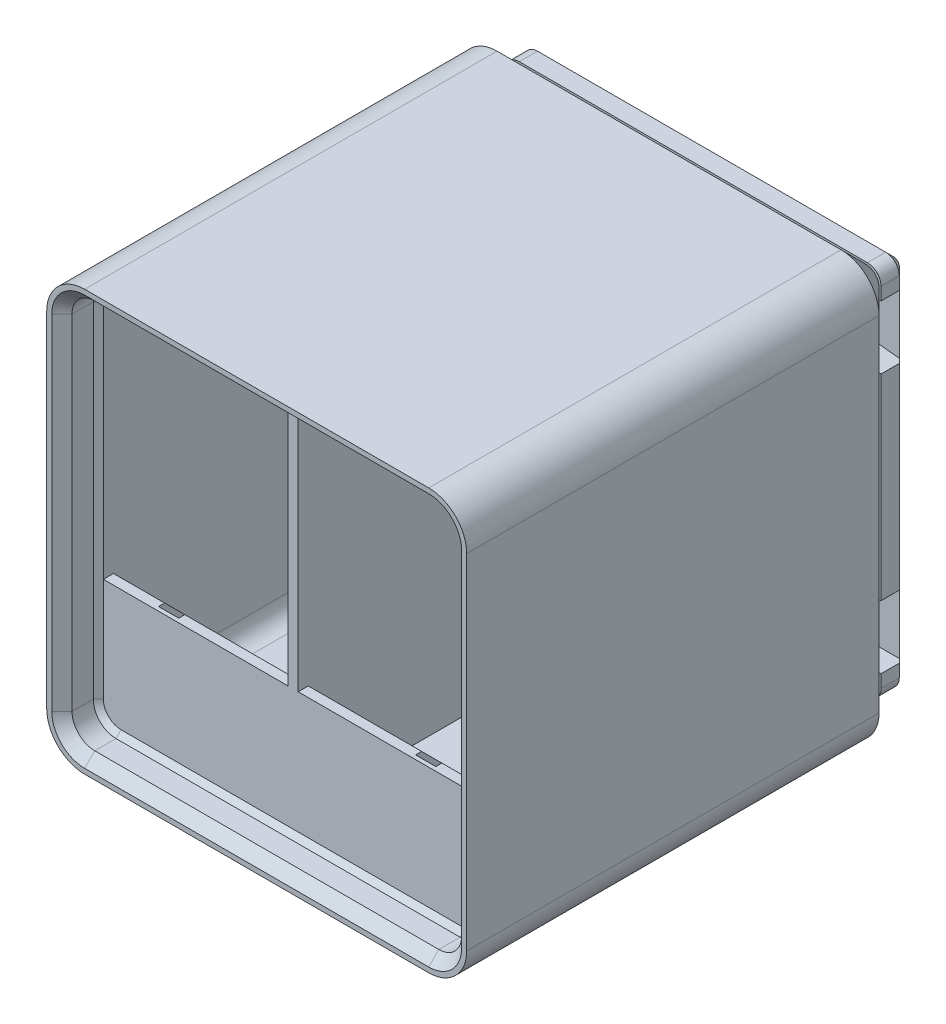
SolidWorks part; units mm, degrees
ref_plane "Front Plane" through (0, 0, 0) normal (0, 0, 1) x (1, 0, 0)
ref_plane "Top Plane" through (0, 0, 0) normal (0, 1, 0) x (1, 0, 0)
ref_plane "Right Plane" through (0, 0, 0) normal (1, 0, 0) x (0, 0, -1)
sketch "Sketch1" plane through (0, 0, 0) normal (0, 0, 1) x (1, 0, 0)
  line L1 (18.55, 18.55) -> (-18.55, 18.55)
  line L2 (18.55, 18.55) -> (18.55, -18.55)
  line L3 (18.55, -18.55) -> (-18.55, -18.55)
  line L4 (-18.55, 18.55) -> (-18.55, -18.55)
  line L5 (18.55, 18.55) -> (-18.55, -18.55) construction
  line L6 (18.55, -18.55) -> (-18.55, 18.55) construction
  point P0 (0, 0)
  dimension "D1" = 37.1
extrude "Boss-Extrude1" add sketch "Sketch1" along normal blind 2.6
sketch "Sketch2" plane through (0, 0, 2.6) normal (0, 0, 1) x (1, 0, 0)
  line L1 (-20.75, 20.75) -> (20.75, 20.75)
  line L2 (-20.75, 20.75) -> (-20.75, -20.75)
  line L3 (-20.75, -20.75) -> (20.75, -20.75)
  line L4 (20.75, 20.75) -> (20.75, -20.75)
  line L5 (-20.75, 20.75) -> (20.75, -20.75) construction
  line L6 (-20.75, -20.75) -> (20.75, 20.75) construction
  point P0 (0, 0)
  dimension "D1" = 41.5
extrude "Boss-Extrude2" add sketch "Sketch2" along normal blind 2.4
sketch "Sketch8" plane through (0, 0, 2.6) normal (0, 0, -1) x (-1, 0, 0)
  line L0 (-18.55, 18.55) -> (-18.55, 5.0094) construction
  line L1 (-18.55, -18.55) -> (-18.55, 18.55) construction
  line L2 (-14.65, 10.1) -> (-18.55, 9.7)
  line L11 (-12.7, 15.95) -> (-18.55, 15.95)
  line L12 (-12.7, 12.7) -> (-12.7, -12.7)
  line L13 (-12.7, -12.7) -> (12.7, -12.7)
  line L14 (12.7, -12.7) -> (12.7, 12.7)
  line L15 (12.7, 12.7) -> (-12.7, 12.7)
  line L16 (-12.7, 9.45) -> (-12.7, -12.7) construction
  line L22 (-18.55, 15.95) -> (-18.55, 9.7)
  arc A0 (-12.7, 15.95) -> (-12.7, 9.45) centre (-12.7, 12.7) cw
  arc A1 (-12.7, 9.45) -> (-14.65, 10.1) centre (-12.7, 12.7) cw
  dimension "D4" = 5.85
  dimension "D5" = 6.25
  dimension "D2" = 6.5
  dimension "D1" = 8.05
extrude "Base Magnet Slot" cut sketch "Sketch8" against normal blind 0.4 and the other way blind 2.2
sketch "Sketch12" plane through (0, 0, 0) normal (0, 0, -1) x (-1, 0, 0)
  line L0 (-12.7, 12.7) -> (-6.2, 12.7) construction
  line L1 (-12.7, 13.7) -> (-6.2, 13.7)
  line L2 (-12.7, 11.7) -> (-6.2, 11.7)
  arc A8 (-14.65, 10.1) -> (-12.7, 15.95) centre (-12.7, 12.7) ccw construction
  arc A9 (-14.65, 10.1) -> (-12.7, 15.95) centre (-12.7, 12.7) ccw construction
  arc A10 (-12.7, 13.7) -> (-12.7, 11.7) centre (-12.7, 12.7) ccw
  arc A11 (-6.2, 11.7) -> (-6.2, 13.7) centre (-6.2, 12.7) ccw
  point P3 (-9.45, 12.7)
  dimension "D1" = 2
  dimension "D2" = 6.5
extrude "Cut-Extrude1" cut sketch "Sketch12" against normal up to surface (2.6 mm away) up to face at (0, 0, 2.6)
mirror "Mirror1" about plane through (0, 0, 0) normal (0, 1, 0) of "Cut-Extrude1", "Base Magnet Slot"
mirror "Mirror2" about plane through (0, 0, 0) normal (1, 0, 0) of "Mirror1"
fillet "Fillet1" radius 1.35 4 edges at (18.55, 18.55, 1.3) (18.55, -18.55, 1.3) (-18.55, -18.55, 1.3) (-18.55, 18.55, 1.3)
fillet "Fillet2" radius 3.75 4 edges at (20.75, -20.75, 3.8) (20.75, 20.75, 3.8) (-20.75, -20.75, 3.8) (-20.75, 20.75, 3.8)
chamfer "Chamfer1" distance 0.8 angle 45 8 edges at (-18.1546, 18.1546, 0) (-18.55, 0, 0) (-18.1546, -18.1546, 0) (0, -18.55, 0) (18.1546, -18.1546, 0) (18.55, 0, 0) (18.1546, 18.1546, 0) (0, 18.55, 0)
chamfer "Chamfer2" distance 2.4 angle 45 8 edges at (20.75, 0, 2.6) (19.6517, 19.6517, 2.6) (19.6517, -19.6517, 2.6) (0, 20.75, 2.6) (0, -20.75, 2.6) (-19.6517, 19.6517, 2.6) (-19.6517, -19.6517, 2.6) (-20.75, 0, 2.6)
sketch "Sketch5" plane through (0, 0, 5) normal (0, 0, 1) x (1, 0, 0)
  line L32 (-17, -18.75) -> (17, -18.75)
  line L33 (18.75, -17) -> (18.75, 17)
  line L42 (17, 18.75) -> (-17, 18.75)
  line L56 (-18.75, 17) -> (-18.75, -17)
  line L57 (-17, -20.75) -> (17, -20.75)
  line L58 (20.75, -17) -> (20.75, 17)
  line L59 (17, 20.75) -> (-17, 20.75)
  line L60 (-20.75, 17) -> (-20.75, -17)
  line L61 (-17, -20.75) -> (17, -20.75)
  line L62 (20.75, -17) -> (20.75, 17)
  line L63 (17, 20.75) -> (-17, 20.75)
  line L64 (-20.75, 17) -> (-20.75, -17)
  arc A24 (17, -18.75) -> (18.75, -17) centre (17, -17) ccw
  arc A25 (18.75, 17) -> (17, 18.75) centre (17, 17) ccw
  arc A26 (-17, 18.75) -> (-18.75, 17) centre (-17, 17) ccw
  arc A27 (-18.75, -17) -> (-17, -18.75) centre (-17, -17) ccw
  arc A30 (17, -20.75) -> (20.75, -17) centre (17, -17) ccw
  arc A31 (20.75, 17) -> (17, 20.75) centre (17, 17) ccw
  arc A32 (-17, 20.75) -> (-20.75, 17) centre (-17, 17) ccw
  arc A33 (-20.75, -17) -> (-17, -20.75) centre (-17, -17) ccw
  arc A34 (17, -20.75) -> (20.75, -17) centre (17, -17) ccw
  arc A35 (20.75, 17) -> (17, 20.75) centre (17, 17) ccw
  arc A36 (-17, 20.75) -> (-20.75, 17) centre (-17, 17) ccw
  arc A37 (-20.75, -17) -> (-17, -20.75) centre (-17, -17) ccw
  dimension "D1" = 0
  dimension "D2" = 2
extrude "Side Walls" add sketch "Sketch5" along normal blind 36.85
sketch "Sketch11" plane through (0, 0, 41.85) normal (0, 0, 1) x (1, 0, 0)
  line L24 (-17, -20.75) -> (17, -20.75) construction
  line L25 (20.75, -17) -> (20.75, 17) construction
  line L26 (17, 20.75) -> (-17, 20.75) construction
  line L27 (-20.75, 17) -> (-20.75, -17) construction
  line L28 (-17, -20.75) -> (17, -20.75)
  line L29 (20.75, -17) -> (20.75, 17)
  line L30 (17, 20.75) -> (-17, 20.75)
  line L31 (-20.75, 17) -> (-20.75, -17)
  line L32 (-17, -19.25) -> (17, -19.25)
  line L33 (19.25, -17) -> (19.25, 17)
  line L34 (17, 19.25) -> (-17, 19.25)
  line L35 (-19.25, 17) -> (-19.25, -17)
  arc A24 (-20.75, -17) -> (-17, -20.75) centre (-17, -17) ccw construction
  arc A25 (17, -20.75) -> (20.75, -17) centre (17, -17) ccw construction
  arc A26 (20.75, 17) -> (17, 20.75) centre (17, 17) ccw construction
  arc A27 (-17, 20.75) -> (-20.75, 17) centre (-17, 17) ccw construction
  arc A28 (-20.75, -17) -> (-17, -20.75) centre (-17, -17) ccw
  arc A29 (17, -20.75) -> (20.75, -17) centre (17, -17) ccw
  arc A30 (20.75, 17) -> (17, 20.75) centre (17, 17) ccw
  arc A31 (-17, 20.75) -> (-20.75, 17) centre (-17, 17) ccw
  arc A32 (17, -19.25) -> (19.25, -17) centre (17, -17) ccw
  arc A33 (19.25, 17) -> (17, 19.25) centre (17, 17) ccw
  arc A34 (-17, 19.25) -> (-19.25, 17) centre (-17, 17) ccw
  arc A35 (-19.25, -17) -> (-17, -19.25) centre (-17, -17) ccw
extrude "Boss-Extrude4" add sketch "Sketch11" along normal blind 3.9
chamfer "Chamfer3" distance 0.8 angle 45 8 edges at (0, -19.25, 41.85) (18.591, -18.591, 41.85) (-18.591, -18.591, 41.85) (19.25, 0, 41.85) (-19.25, 0, 41.85) (18.591, 18.591, 41.85) (-18.591, 18.591, 41.85) (0, 19.25, 41.85)
chamfer "Chamfer4" distance 1 angle 45 8 edges at (0, -19.25, 45.75) (18.591, -18.591, 45.75) (-18.591, -18.591, 45.75) (19.25, 0, 45.75) (-19.25, 0, 45.75) (18.591, 18.591, 45.75) (-18.591, 18.591, 45.75) (0, 19.25, 45.75)
sketch "Sketch13" plane through (18.75, 0, 0) normal (-1, 0, 0) x (0, 0, 1)
  line L0 (5, -17) -> (5, 17) construction
  line L1 (42.15, 18.75) -> (5, 18.75) construction
  line L2 (5, -1.25) -> (5, 18.75)
  line L3 (25, 18.75) -> (5, 18.75)
  arc A0 (25, 18.75) -> (5, -1.25) centre (25, -1.25) ccw
  dimension "D1" = 20
extrude "Internal Ramp" add sketch "Sketch13" along normal up to surface (37.5 mm away) up to face at (-18.75, 0, 23.575)
ref_plane "Plane1" through (0, 0, 42.15) normal (0, 0, -1) x (-1, 0, 0)
sketch "Sketch14" plane through (0, 0, 42.15) normal (0, 0, -1) x (-1, 0, 0)
  line L0 (-18.75, -17) -> (-18.75, 17) construction
  line L1 (17, -18.75) -> (-17, -18.75) construction
  line L2 (18.75, 17) -> (18.75, -17) construction
  line L3 (-18.75, -17) -> (-18.75, -6.75)
  line L4 (17, -18.75) -> (-17, -18.75)
  line L5 (18.75, -6.75) -> (18.75, -17)
  line L6 (-18.75, -6.75) -> (18.75, -6.75)
  arc A0 (-18.75, -17) -> (-17, -18.75) centre (-17, -17) ccw construction
  arc A1 (17, -18.75) -> (18.75, -17) centre (17, -17) ccw construction
  arc A2 (-18.75, -17) -> (-17, -18.75) centre (-17, -17) ccw
  arc A3 (17, -18.75) -> (18.75, -17) centre (17, -17) ccw
  dimension "D1" = 12
extrude "Boss-Extrude6" add sketch "Sketch14" along normal blind 12
chamfer "Chamfer5" distance 11 angle 45 1 edges at (0, -6.75, 30.15)
ref_plane "Offset Plane" through (0, 0, 41.75) normal (0, 0, 1) x (1, 0, 0)
sketch "Sketch17" plane through (0, 0, 41.75) normal (0, 0, 1) x (1, 0, 0)
  line L0 (-17, -20.75) -> (17, -20.75) construction
  line L1 (-17, -20.75) -> (17, -20.75) construction
  line L2 (-20.75, -12.7) -> (20.75, -12.7) construction
  line L3 (-20.75, 17) -> (-20.75, -17) construction
  line L4 (20.75, -17) -> (20.75, 17) construction
  line L5 (-20.75, 17) -> (-20.75, -17) construction
  line L6 (-12.7, -11.0494) -> (-12.7, 18.75) construction
  line L7 (-17, 18.75) -> (17, 18.75) construction
  line L8 (-15.95, -12.7) -> (-15.95, -20.75)
  line L9 (-15.95, -20.75) -> (-9.45, -20.75)
  line L10 (-10.1, -14.65) -> (-9.45, -20.75)
  line L11 (-12.7, -12.7) -> (-12.7, -4.7) construction
  line L13 (-13.7, -9.6077) -> (-13.7, -4.7)
  line L14 (-11.7, -9.6077) -> (-11.7, -4.7)
  arc A0 (-15.95, -12.7) -> (-13.7, -9.6077) centre (-12.7, -12.7) cw
  arc A2 (-11.7, -4.7) -> (-13.7, -4.7) centre (-12.7, -4.7) ccw
  arc A3 (-11.7, -9.6077) -> (-10.1, -14.65) centre (-12.7, -12.7) cw
  point P20 (-12.7, -8.7)
  dimension "D3" = 3.25
  dimension "D1" = 8.05
  dimension "D2" = 8.05
  dimension "D4" = 6.5
  dimension "D5" = 5.85
extrude "Cut-Extrude2" cut sketch "Sketch17" against normal blind 2.6
mirror "Mirror3" about plane through (0, 0, 0) normal (1, 0, 0) of "Cut-Extrude2"
sketch "Sketch18" plane through (0, 0, 0) normal (1, 0, 0) x (0, 0, -1)
  line L0 (-42.15, 18.75) -> (-42.15, 17) construction
  line L1 (-42.15, 18.75) -> (-25, 18.75) construction
  line L2 (-42.15, 18.75) -> (-42.15, 17)
  line L3 (-42.15, 18.75) -> (-25, 18.75)
  line L6 (-42.15, 17) -> (-42.15, -6.75)
  line L7 (-42.15, -6.75) -> (-41.15, -6.75)
  line L8 (-41.15, -6.75) -> (-30.9, -17)
  line L9 (-30.9, -17) -> (-5, -17)
  line L10 (-5, -17) -> (-5, -1.25)
  line L11 (-16.8185, 17) -> (-42.15, 17)
  line L12 (-42.15, 17) -> (-42.15, -6.75)
  line L13 (-42.15, -6.75) -> (-41.15, -6.75)
  line L14 (-41.15, -6.75) -> (-30.9, -17)
  line L15 (-30.9, -17) -> (-5, -17)
  line L16 (-5, -17) -> (-5, -1.25)
  arc A0 (-16.8185, 17) -> (-25, 18.75) centre (-25, -1.25) ccw construction
  arc A1 (-5, -1.25) -> (-16.8185, 17) centre (-25, -1.25) ccw
  arc A3 (-5, -1.25) -> (-16.8185, 17) centre (-25, -1.25) ccw construction
  arc A4 (-16.8185, 17) -> (-25, 18.75) centre (-25, -1.25) ccw
  arc A5 (-5, -1.25) -> (-16.8185, 17) centre (-25, -1.25) ccw
  dimension "D1" = 0
extrude "Split Wall" add sketch "Sketch18" along normal mid plane 1
equation "\"MagnetHoleDia\"= 6.5"
equation "\"MagnetPressGap\"= 5.85"
equation "\"MagnetSlotDepth\"= 2.6"
equation "\"D2@Sketch17\"=\"D1@Sketch17\""
equation "\"D3@Sketch17\"=\"MagnetHoleDia\"/2"
